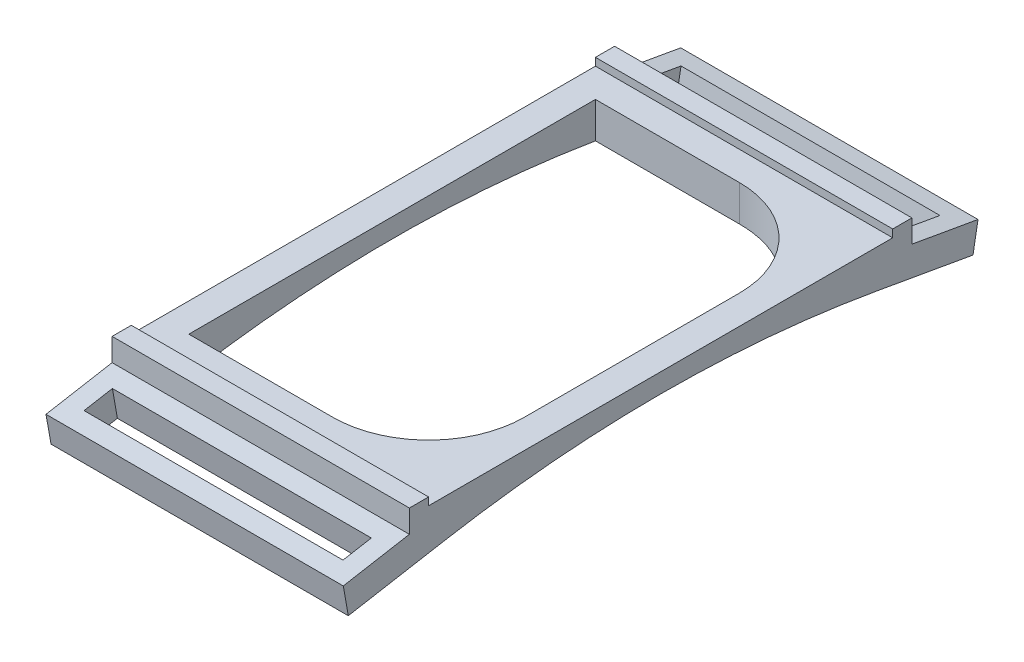
SolidWorks part; units mm, degrees
ref_plane "Front Plane" through (0, 0, 0) normal (0, 0, 1) x (1, 0, 0)
ref_plane "Top Plane" through (0, 0, 0) normal (0, 1, 0) x (1, 0, 0)
ref_plane "Right Plane" through (0, 0, 0) normal (1, 0, 0) x (0, 0, -1)
ref_axis "X Axis" through (-88.99, 0, 0) along (1, 0, 0)
ref_axis "Y Axis" through (0, 55, 0) along (0, -1, 0)
ref_axis "Z Axis" through (0, 0, -88.99) along (0, 0, 1)
sketch "Sketch1" plane through (0, 0, 0) normal (1, 0, 0) x (0, 0, -1)
  line L0 (0, 0) -> (0, -2) construction
  line L1 (-24.2, 0) -> (24.2, 0)
  line L2 (24.2, 0) -> (24.2, 0.8)
  line L6 (26.2, 0.8) -> (26.2, -1.5746)
  line L7 (26.2, -1.5746) -> (33.0937, -2.7902)
  line L8 (33.0937, -2.7902) -> (32.5727, -5.7446)
  line L9 (32.5727, -5.7446) -> (22.5, -3.9685)
  line L10 (-32.5727, -5.7446) -> (-22.5, -3.9685)
  line L11 (-33.0937, -2.7902) -> (-32.5727, -5.7446)
  line L12 (-26.2, -1.5746) -> (-33.0937, -2.7902)
  line L13 (-26.2, 0.8) -> (-26.2, -1.5746)
  line L17 (-24.2, 0) -> (-24.2, 0.8)
  line L18 (24.2, 0.8) -> (26.2, 0.8)
  line L19 (-24.2, 0.8) -> (-26.2, 0.8)
  line L20 (31.124, -2.4429) -> (30.6031, -5.3973) construction
  arc A0 (22.5, -3.9685) -> (-22.5, -3.9685) centre (0, -131.5723) ccw
  dimension "D1" = 3
  dimension "D2" = 48.4
  dimension "D3" = 0.8
  dimension "D4" = 2
  dimension "D5" = 2
  dimension "D6" = 2
  dimension "D7" = 45
  dimension "D8" = 80
  dimension "D9" = 5
extrude "Boss-Extrude1" add sketch "Sketch1" along normal blind 31
sketch "Sketch2" plane through (0, 2.9533, -0.5207) normal (0, 0.9848, -0.1736) x (1, 0, 0)
  line L0 (2, 31.0754) -> (2, 28.0754)
  line L1 (2, 28.0754) -> (29, 28.0754)
  line L2 (29, 28.0754) -> (29, 31.0754)
  line L3 (29, 31.0754) -> (2, 31.0754)
  line L4 (0, 33.0754) -> (0, 26.0754)
  line L5 (0, 26.0754) -> (31, 26.0754)
  line L6 (31, 26.0754) -> (31, 33.0754)
  line L7 (31, 33.0754) -> (0, 33.0754)
  line L8 (0, 33.0754) -> (0, 26.0754) construction
  line L9 (0, 26.0754) -> (31, 26.0754) construction
  line L10 (31, 26.0754) -> (31, 33.0754) construction
  line L11 (31, 33.0754) -> (0, 33.0754) construction
  dimension "D1" = 0
  dimension "D2" = 2
extrude "Cut-Extrude1" cut sketch "Sketch2" against normal through all
mirror "Mirror1" about plane through (0, 0, 0) normal (0, 0, 1) of "Cut-Extrude1"
sketch "Sketch3" plane through (0, 0, 0) normal (0, 1, 0) x (1, 0, 0)
  line L0 (3, 21.2) -> (3, -21.2)
  line L1 (3, -21.2) -> (28, -21.2)
  line L2 (28, -21.2) -> (28, 21.2)
  line L3 (28, 21.2) -> (3, 21.2)
  line L4 (0, 24.2) -> (0, -24.2)
  line L5 (0, -24.2) -> (31, -24.2)
  line L6 (31, -24.2) -> (31, 24.2)
  line L7 (31, 24.2) -> (0, 24.2)
  line L8 (0, 24.2) -> (0, -24.2) construction
  line L9 (0, -24.2) -> (31, -24.2) construction
  line L10 (31, -24.2) -> (31, 24.2) construction
  line L11 (31, 24.2) -> (0, 24.2) construction
  dimension "D1" = 0
  dimension "D2" = 3
extrude "Cut-Extrude2" cut sketch "Sketch3" against normal through all
fillet "Fillet1" radius 10 2 edges at (28, -1.873, -21.2) (28, -1.873, 21.2)
